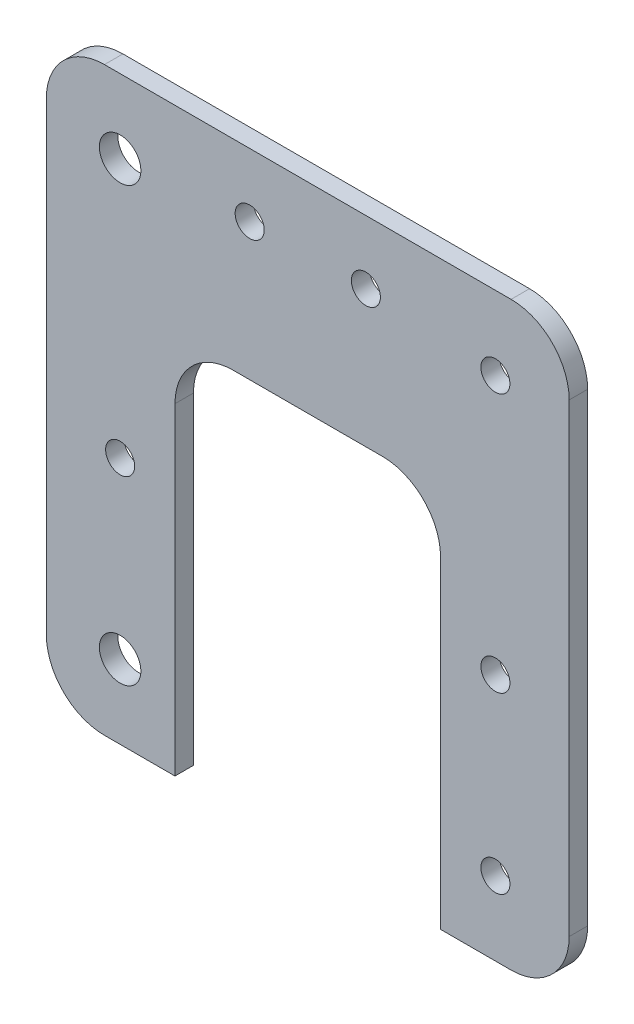
SolidWorks part; units mm, degrees
ref_plane "Front Plane" through (0, 0, 0) normal (0, 0, 1) x (1, 0, 0)
ref_plane "Top Plane" through (0, 0, 0) normal (0, 1, 0) x (1, 0, 0)
ref_plane "Right Plane" through (0, 0, 0) normal (1, 0, 0) x (0, 0, -1)
sketch "Sketch1" plane through (0, 0, 0) normal (0, 0, 1) x (1, 0, 0)
  line L1 (-45, -55) -> (45, -55)
  line L2 (-45, -55) -> (-45, 45)
  line L3 (-45, 45) -> (45, 45)
  line L4 (45, -55) -> (45, 45)
  line L8 (-32.3, 32.3) -> (-32.3, -42.3) construction
  line L9 (-32.3, -42.3) -> (32.3, -42.3) construction
  line L10 (32.3, -42.3) -> (32.3, 32.3) construction
  line L11 (32.3, 32.3) -> (-32.3, 32.3) construction
  line L12 (32.3, -12.3) -> (-32.3, -12.3) construction
  circle A4 centre (32.3, -12.3) radius 2.5
  circle A5 centre (32.3, -42.3) radius 2.5
  circle A6 centre (-32.3, -42.3) radius 3.57
  circle A7 centre (-32.3, -12.3) radius 2.5
  circle A9 centre (-32.3, 32.3) radius 3.57
  circle A11 centre (32.3, 32.3) radius 2.5
  dimension "D9" = 7.14
  dimension "D10" = 5
  dimension "D1" = 90
  dimension "D2" = 100
  dimension "D3" = 12.7
  dimension "D4" = 12.7
  dimension "D5" = 42.7
  dimension "D6" = 12.7
  dimension "D7" = 45
  dimension "D8" = 45
  dimension "D11" = 12.7
extrude "Boss-Extrude1" add sketch "Sketch1" against normal blind 3.18 from offset 19.16
sketch "Sketch2" plane through (0, 0, 15.98) normal (0, 0, -1) x (-1, 0, 0)
  line L0 (45, -55) -> (-45, -55) construction
  line L1 (-22.86, -55) -> (22.86, -55)
  line L2 (-22.86, -55) -> (-22.86, 10.5119)
  line L3 (-22.86, 10.5119) -> (22.86, 10.5119)
  line L4 (22.86, -55) -> (22.86, 10.5119)
  line L5 (0, 0) -> (0, 10.5119) construction
  dimension "D1" = 45.72
extrude "Cut-Extrude1" cut sketch "Sketch2" against normal through all
fillet "Fillet1" radius 10 6 edges at (45, -55, 17.57) (-45, -55, 17.57) (-45, 45, 17.57) (45, 45, 17.57) (-22.86, 10.5119, 17.57) (22.86, 10.5119, 17.57)
ref_plane "Midplane" through (0, -5, 0) normal (0, 1, 0) x (1, 0, 0)
sketch "Sketch3" plane through (0, 0, 19.16) normal (0, 0, 1) x (1, 0, 0)
  circle A0 centre (10, 34.0691) radius 2.5 construction
  circle A1 centre (-10, 34.0691) radius 2.5 construction
  circle A2 centre (10, 34.0691) radius 2.5
  circle A3 centre (-10, 34.0691) radius 2.5
extrude "Cut-Extrude2" cut sketch "Sketch3" against normal through all
